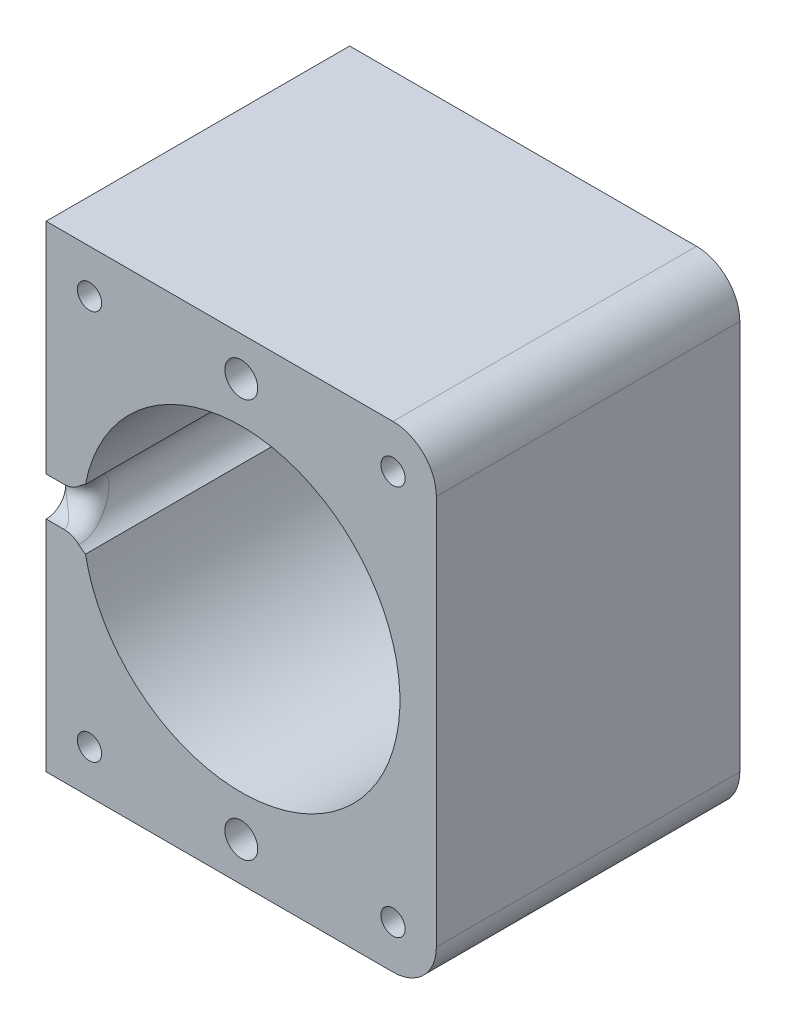
SolidWorks part; units mm, degrees
ref_plane "Front Plane" through (0, 0, 0) normal (1, 0, 0) x (0, 1, 0)
ref_plane "Top Plane" through (0, 0, 0) normal (0, 0, 1) x (0, 1, 0)
ref_plane "Right Plane" through (0, 0, 0) normal (0, 1, 0) x (-1, 0, 0)
sketch "Sketch1" plane through (0, 0, 0) normal (0, 0, 1) x (0, 1, 0)
  line L1 (0, 0) -> (55, 0)
  line L2 (0, 0) -> (0, 45)
  line L3 (0, 45) -> (55, 45)
  line L4 (55, 0) -> (55, 45)
  dimension "D1" = 55
  dimension "D2" = 45
extrude "Boss-Extrude1" add sketch "Sketch1" along normal blind 35
sketch "Sketch2" plane through (0, 0, 35) normal (0, 0, 1) x (1, 0, 0)
  line L0 (-22.5, 55) -> (-22.5, 0) construction
  line L1 (0, 55) -> (-45, 55) construction
  line L2 (-45, 0) -> (0, 0) construction
  circle A0 centre (-22.5, 27.5) radius 18.3
  dimension "D1" = 36.6
extrude "Cut-Extrude1" cut sketch "Sketch2" against normal blind 32
sketch "Sketch3" plane through (0, 0, 35) normal (0, 0, 1) x (1, 0, 0)
  line L0 (-45, 27.5) -> (-38.5, 27.5) construction
  line L1 (-45, 55) -> (-45, 0) construction
  circle A1 centre (-38.5, 27.5) radius 4
  dimension "D1" = 8
  dimension "D2" = 6.5
extrude "Cut-Extrude2" cut sketch "Sketch3" against normal blind 32
sketch "Sketch4" plane through (0, 0, 35) normal (0, 0, 1) x (1, 0, 0)
  line L0 (-22.5, 55) -> (-22.5, 0) construction
  line L1 (0, 55) -> (-45, 55) construction
  line L2 (-45, 0) -> (0, 0) construction
  circle A0 centre (-22.5, 4.5) radius 1.9
  circle A1 centre (-22.5, 50.5) radius 1.9
  point P10 (-22.5, 27.5)
  dimension "D3" = 3.8
  dimension "D1" = 23
  dimension "D2" = 23
extrude "Cut-Extrude3" cut sketch "Sketch4" against normal blind 20
sketch "Sketch5" plane through (0, 0, 35) normal (0, 0, 1) x (1, 0, 0)
  line L0 (-45, 50) -> (0, 50) construction
  line L1 (-45, 55) -> (-45, 0) construction
  line L2 (0, 0) -> (0, 55) construction
  line L3 (-45, 5) -> (0, 5) construction
  line L4 (0, 55) -> (-45, 55) construction
  line L5 (-45, 0) -> (0, 0) construction
  line L6 (-40, 50) -> (-40, 5) construction
  line L7 (-5, 50) -> (-5, 5) construction
  circle A0 centre (-40, 50) radius 1.4
  circle A1 centre (-5, 50) radius 1.4
  circle A2 centre (-5, 5) radius 1.4
  circle A3 centre (-40, 5) radius 1.4
  dimension "D1" = 2.8
  dimension "D2" = 5
  dimension "D3" = 5
  dimension "D4" = 5
  dimension "D5" = 5
extrude "Cut-Extrude4" cut sketch "Sketch5" against normal blind 15
fillet "Fillet1" radius 5 2 edges at (0, 55, 17.5) (0, 0, 17.5)
sketch "Sketch6" plane through (-45, 0, 0) normal (-1, 0, 0) x (0, -1, 0)
  line L0 (-55, 5) -> (0, 5) construction
  line L1 (-55, 35) -> (-55, 0) construction
  line L2 (0, 35) -> (0, 0) construction
  line L3 (-55, 25) -> (0, 25) construction
  line L4 (-55, 0) -> (0, 0) construction
  circle A0 centre (-50, 25) radius 1.9
  circle A1 centre (-5, 25) radius 1.9
  circle A2 centre (-5, 5) radius 1.9
  circle A3 centre (-50, 5) radius 1.9
  dimension "D3" = 3.8
  dimension "D1" = 5
  dimension "D2" = 20
  dimension "D4" = 5
  dimension "D5" = 5
  dimension "D6" = 5
  dimension "D7" = 5
extrude "Cut-Extrude5" cut sketch "Sketch6" against normal blind 15
sketch "Sketch7" plane through (-45, 0, 0) normal (-1, 0, 0) x (0, -1, 0)
  line L0 (-55, 35) -> (0, 35) construction
  circle A0 centre (-27.5, 35) radius 2.25
  dimension "D1" = 4.5
extrude "Cut-Extrude6" cut sketch "Sketch7" against normal up to next
fillet "Fillet2" radius 2.5 1 edges at (-42.4987, 27.6011, 32.7523)
